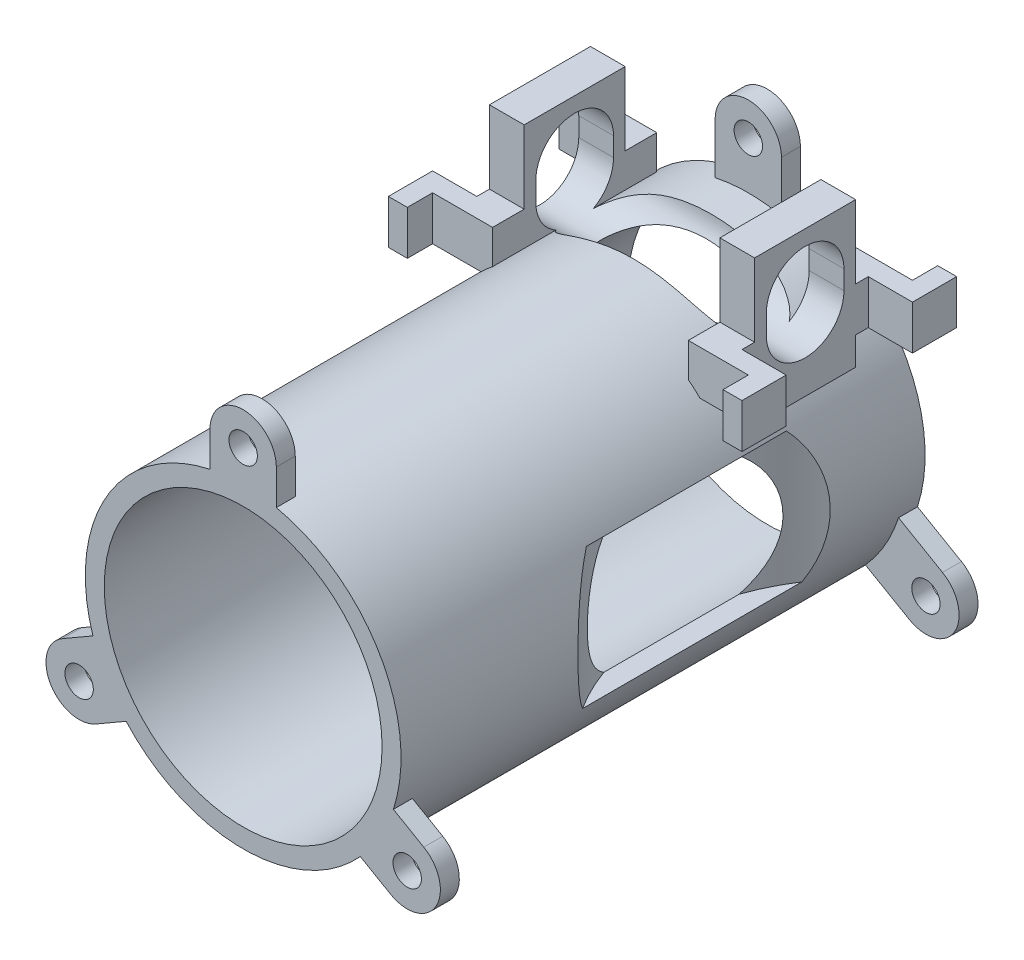
SolidWorks part; units mm, degrees
ref_plane "Front Plane" through (0, 0, 0) normal (0, 0, 1) x (1, 0, 0)
ref_plane "Top Plane" through (0, 0, 0) normal (0, 1, 0) x (1, 0, 0)
ref_plane "Right Plane" through (0, 0, 0) normal (1, 0, 0) x (0, 0, -1)
sketch "Sketch1" plane through (0, 0, 0) normal (0, 0, 1) x (1, 0, 0)
  circle A0 centre (0, 0) radius 22
  circle A1 centre (0, 0) radius 25
  dimension "D1" = 44
  dimension "D2" = 3
extrude "Boss-Extrude1" add sketch "Sketch1" along normal blind 30
ref_plane "Plane1" through (0, 0, 15) normal (0, 0, 1) x (1, 0, 0)
sketch "Sketch3" plane through (0, 0, 0) normal (1, 0, 0) x (0, 0, -1)
  line L0 (0, 25) -> (-30, 25) construction
  circle A0 centre (-15, 25) radius 6.15
  dimension "D1" = 12.3
extrude "Cut-Extrude1" cut sketch "Sketch3" against normal mid plane 50
sketch "Sketch7" plane through (0, 0, 30) normal (0, 0, 1) x (1, 0, 0)
  circle A0 centre (0, 0) radius 22
  circle A1 centre (0, 0) radius 25
extrude "Boss-Extrude4" add sketch "Sketch7" along normal blind 53
ref_plane "Plane2" through (-25, 0, 0) normal (-1, 0, 0) x (0, 0, 1)
sketch "Sketch9" plane through (0, 0, 0) normal (0, 0, -1) x (-1, 0, 0)
  line L0 (0, 0) -> (0, 32.4847) construction
  line L1 (-5.25, 32.4847) -> (-5.25, 24.4425)
  line L2 (5.25, 32.4847) -> (5.25, 24.4425)
  circle A0 centre (0, 32.4847) radius 2.25
  circle A1 centre (0, 32.4847) radius 5.25
  circle A2 centre (0, 0) radius 25 construction
  arc A3 (-5.25, 24.4425) -> (5.25, 24.4425) centre (0, 0) cw
  circle A6 centre (0, 32.4847) radius 2.25 construction
  circle M3 centre (0, 0) radius 25
  dimension "D1" = 4.5
  dimension "D2" = 3
extrude "Boss-Extrude5" add sketch "Sketch9" against normal blind 3 contours A1 L1 M3 | A1 A3 A0 M3 | A1 L2 M3 region at (0, 26.7779, 0) region at (0, 37.5862, 0)
pattern_circular "CirPattern1" count 3 over 360 about axis through (0, 0, 0) along (0, 0, 1) of "Boss-Extrude5"
sketch "Sketch10" plane through (0, 0, 83) normal (0, 0, 1) x (1, 0, 0)
  line L0 (-5.25, 30) -> (-5.25, 24.4425)
  line L1 (5.25, 30) -> (5.25, 24.4425)
  line L2 (0, 0) -> (0, 30) construction
  circle A0 centre (0, 30) radius 2.25
  circle A1 centre (0, 30) radius 5.25
  arc A2 (-5.25, 24.4425) -> (5.25, 24.4425) centre (0, 0) cw
  circle A3 centre (0, 0) radius 25 construction
  circle M5 centre (0, 0) radius 25
  dimension "D2" = 4.5
  dimension "D3" = 30
  dimension "D1" = 3
extrude "Boss-Extrude6" add sketch "Sketch10" against normal blind 3 contours A1 A0 M5 | A1 L0 M5 | A1 L1 M5 region at (-4.234, 25.9338, 83) region at (0, 35.103, 83) region at (4.234, 25.9338, 83)
pattern_circular "CirPattern2" count 3 every 120 about axis through (0, 0, 83) along (0, 0, 1) of "Boss-Extrude6"
ref_plane "Plane3" through (0, 11.51, 0) normal (0, 1, 0) x (1, 0, 0)
sketch "Sketch14" plane through (0, 0, 15) normal (0, 0, 1) x (1, 0, 0)
  line L0 (-21, 13.5647) -> (-21, 36.5647)
  line L1 (-21, 36.5647) -> (-15.5, 36.5647)
  line L2 (-15.5, 36.5647) -> (-15.5, 19.615)
  line L3 (-25, 27.5) -> (-25, -27.5) construction
  arc A0 (-5.25, 24.4425) -> (-23.7929, -7.6746) centre (0, 0) ccw construction
  arc A1 (-15.5, 19.615) -> (-21, 13.5647) centre (0, 0) ccw
  dimension "D1" = 23
  dimension "D2" = 4
  dimension "D3" = 5.5
extrude "Boss-Extrude7" add sketch "Sketch14" along normal mid plane 16
sketch "Sketch15" plane through (-21, 0, 0) normal (-1, 0, 0) x (0, 0, 1)
  line L0 (15, 25) -> (15, 28) construction
  line L1 (15, -27.5) -> (15, 27.5) construction
  line L2 (8.85, 25) -> (8.85, 28)
  line L3 (21.15, 25) -> (21.15, 28)
  line L4 (80, 25) -> (21.15, 25) construction
  arc A0 (8.85, 25) -> (21.15, 25) centre (15, 25) ccw
  arc A1 (21.15, 28) -> (8.85, 28) centre (15, 28) ccw
  point P4 (15, 26.5)
  dimension "D1" = 6.15
  dimension "D2" = 3
extrude "Cut-Extrude5" cut sketch "Sketch15" against normal blind 16
ref_plane "Plane5" through (0, 25, 0) normal (0, 1, 0) x (1, 0, 0)
sketch "Sketch17" plane through (0, 25, 0) normal (0, 1, 0) x (1, 0, 0)
  line L1 (-15.5, -23) -> (-21, -23)
  line L2 (-15.5, -23) -> (-15.5, -25)
  line L3 (-15.5, -25) -> (-21, -25)
  line L4 (-21, -23) -> (-21, -25)
  line L5 (-15.5, -23) -> (-21, -25) construction
  line L6 (-15.5, -25) -> (-21, -23) construction
  line L7 (-15.5, -25) -> (-28, -25)
  line L8 (-15.5, -25) -> (-15.5, -28)
  line L9 (-15.5, -28) -> (-28, -28)
  line L10 (-28, -25) -> (-28, -28)
  line L11 (-15.5, -25) -> (-28, -28) construction
  line L12 (-15.5, -28) -> (-28, -25) construction
  line L13 (-28, -28) -> (-25, -28)
  line L14 (-28, -28) -> (-28, -32)
  line L15 (-28, -32) -> (-25, -32)
  line L16 (-25, -28) -> (-25, -32)
  line L17 (-28, -28) -> (-25, -32) construction
  line L18 (-28, -32) -> (-25, -28) construction
  point P4 (-18.25, -24)
  point P10 (-21.75, -26.5)
  point P14 (-26.5, -30)
  point P15 (0, 0)
  dimension "D1" = 2
  dimension "D2" = 3
  dimension "D3" = 4
  dimension "D4" = 4
extrude "Boss-Extrude8" add sketch "Sketch17" against normal blind 7 contours L16 L9 L14 L15 | L7 L10 L9 L8 L3 | L1 L4 L3 L2 region at (-18.25, 25, 24) region at (-21.75, 25, 26.5) region at (-26.5, 25, 30)
mirror "Mirror1" about plane through (0, 0, 15) normal (0, 0, 1) of "Boss-Extrude8"
mirror "Mirror2" about plane through (0, 0, 0) normal (1, 0, 0) of "Mirror1", "Boss-Extrude8", "Cut-Extrude5", "Boss-Extrude7"
sketch "Sketch12" plane through (0, 11.51, 0) normal (0, 1, 0) x (1, 0, 0)
  line L0 (0, -44.5194) -> (0, -33.7673) construction
  line L1 (-25.5075, 0) -> (-33.3825, 0) construction
  circle A0 centre (-50, -35) radius 30
  circle A1 centre (50, -35) radius 30
  circle A2 centre (-50, -35) radius 32
  circle A3 centre (50, -35) radius 32
  dimension "D1" = 60
  dimension "D2" = 100
  dimension "D3" = 35
  dimension "D4" = 2
extrude "Cut-Extrude4" cut sketch "Sketch12" against normal blind 21 contours A2 A0 | A1 | A3 A1 | A0 region at (50, 11.51, 35) region at (-81.0949, 11.51, 35) region at (18.9051, 11.51, 35)
